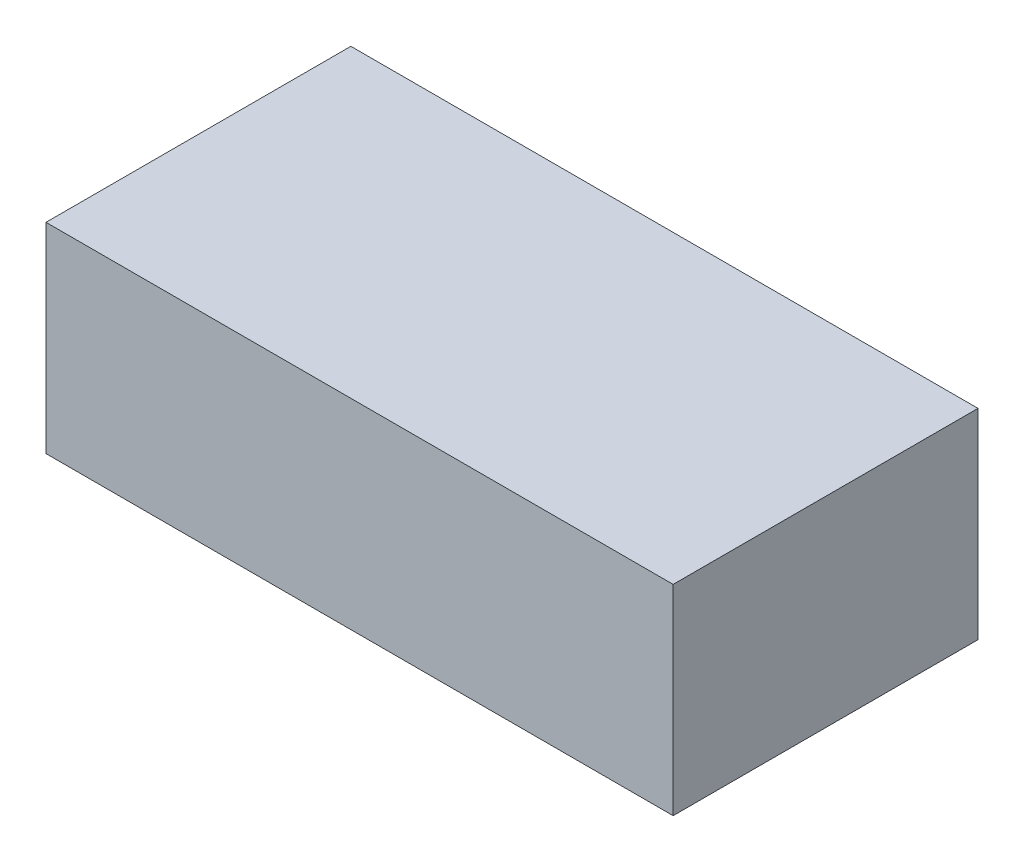
SolidWorks part; units mm, degrees
ref_plane "Front Plane" through (0, 0, 0) normal (0, 0, 1) x (1, 0, 0)
ref_plane "Top Plane" through (0, 0, 0) normal (0, 1, 0) x (1, 0, 0)
ref_plane "Right Plane" through (0, 0, 0) normal (1, 0, 0) x (0, 0, -1)
sketch "Sketch1" plane through (0, 0, 0) normal (0, 1, 0) x (1, 0, 0)
  line L1 (-36, 17.5) -> (36, 17.5)
  line L2 (-36, 17.5) -> (-36, -17.5)
  line L3 (-36, -17.5) -> (36, -17.5)
  line L4 (36, 17.5) -> (36, -17.5)
  line L5 (-36, 17.5) -> (36, -17.5) construction
  line L6 (-36, -17.5) -> (36, 17.5) construction
  point P0 (0, 0)
  dimension "D1" = 72
  dimension "D2" = 35
extrude "Boss-Extrude1" add sketch "Sketch1" along normal blind 23
